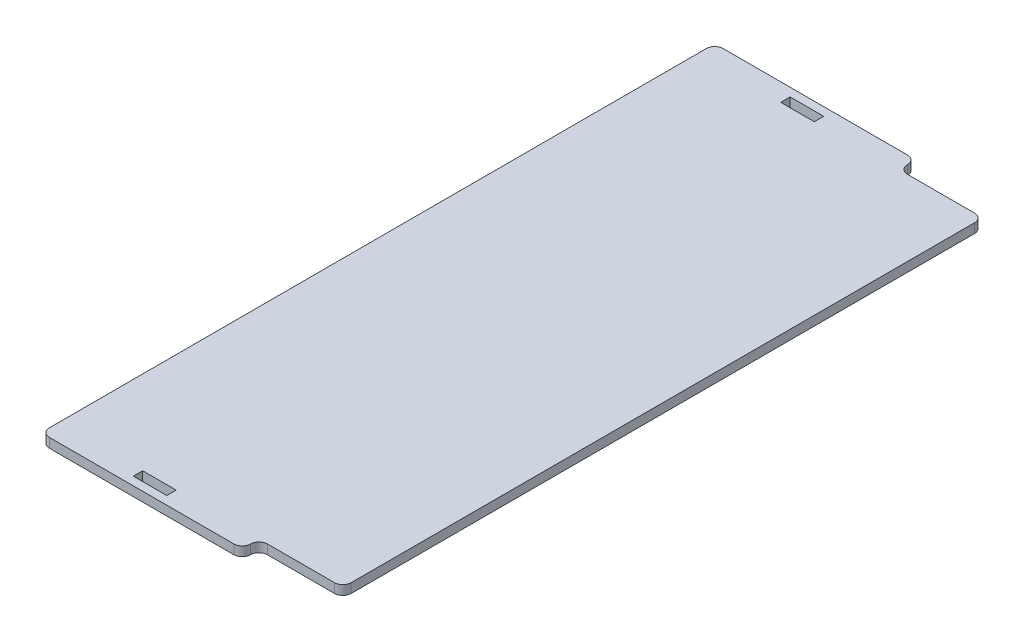
SolidWorks part; units mm, degrees
material "t5ハニカムプラダン"
ref_plane "正面" through (0, 0, 0) normal (0, 0, 1) x (1, 0, 0)
ref_plane "平面" through (0, 0, 0) normal (0, 1, 0) x (1, 0, 0)
ref_plane "右側面" through (0, 0, 0) normal (1, 0, 0) x (0, 0, -1)
sketch "ｽｹｯﾁ1" plane through (0, 0, 0) normal (0, 1, 0) x (1, 0, 0)
  line L0 (0, -200.9) -> (0, 0) construction
  line L1 (-60, 200.9) -> (60, 200.9)
  line L2 (-60, 200.9) -> (-60, -200.9)
  line L3 (-60, -200.9) -> (60, -200.9)
  line L4 (60, 200.9) -> (60, 190.9)
  line L5 (-60, 200.9) -> (60, -200.9) construction
  line L6 (-60, -200.9) -> (60, 200.9) construction
  line L7 (0, 0) -> (50, 0) construction
  line L8 (-10, 195.9) -> (10, 190.3) construction
  line L9 (-10, -190.3) -> (10, -190.3)
  line L10 (-10, -190.3) -> (-10, -195.9)
  line L11 (-10, -195.9) -> (10, -195.9)
  line L12 (10, -190.3) -> (10, -195.9)
  line L13 (-10, -190.3) -> (10, -195.9) construction
  line L14 (-10, -195.9) -> (10, -190.3) construction
  line L15 (-10, 190.3) -> (10, 195.9) construction
  line L16 (10, 190.3) -> (10, 195.9)
  line L17 (-10, 195.9) -> (10, 195.9)
  line L18 (-10, 190.3) -> (-10, 195.9)
  line L19 (-10, 190.3) -> (10, 190.3)
  line L20 (50, 0) -> (85, 0) construction
  line L21 (60, -190.9) -> (60, -200.9)
  line L22 (110, 190.9) -> (60, 190.9)
  line L23 (110, 190.9) -> (110, -190.9)
  line L24 (110, -190.9) -> (60, -190.9)
  line L26 (110, 190.9) -> (60, -190.9) construction
  line L27 (110, -190.9) -> (60, 190.9) construction
  point P0 (0, 0)
  point P9 (0, -193.1)
  point P18 (0, 193.1)
  dimension "D1" = 401.8
  dimension "D2" = 120
  dimension "D3" = 20
  dimension "D4" = 5.6
  dimension "D5" = 5
  dimension "D6" = 50
  dimension "D7" = 10
extrude "ﾎﾞｽ - 押し出し1" add sketch "ｽｹｯﾁ1" along normal blind 5.6
fillet "ﾌｨﾚｯﾄ1" radius 5 8 edges at (-60, 2.8, -200.9) (60, 2.8, -200.9) (-60, 2.8, 200.9) (60, 2.8, -190.9) (110, 2.8, -190.9) (110, 2.8, 190.9) (60, 2.8, 190.9) (60, 2.8, 200.9)
